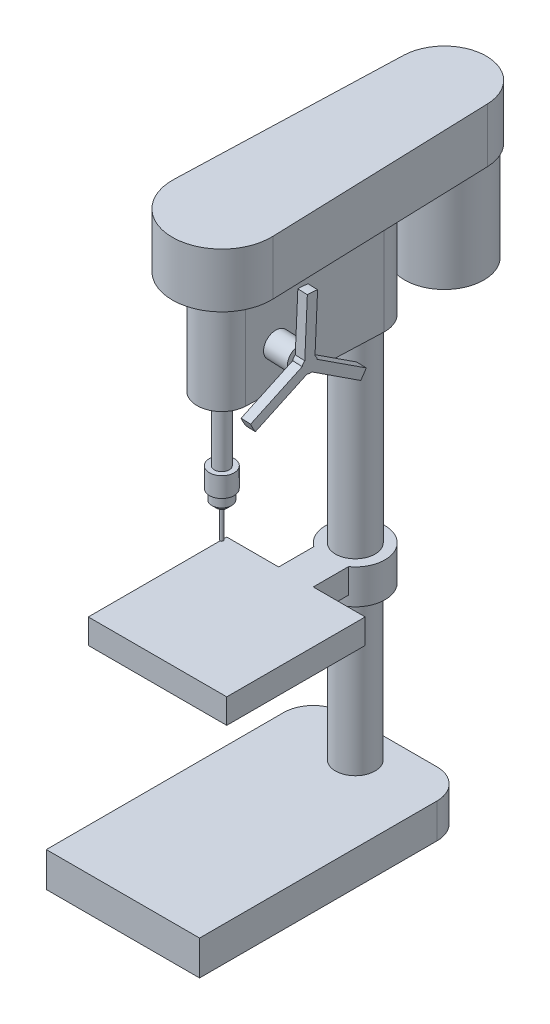
SolidWorks part; units mm, degrees
ref_plane "正面" through (0, 0, 0) normal (0, 0, 1) x (1, 0, 0)
ref_plane "平面" through (0, 0, 0) normal (0, 1, 0) x (1, 0, 0)
ref_plane "右側面" through (0, 0, 0) normal (1, 0, 0) x (0, 0, -1)
sketch "ｽｹｯﾁ1" plane through (0, 0, 0) normal (0, 1, 0) x (1, 0, 0)
  line L1 (0, 0) -> (310, 0)
  line L2 (0, 0) -> (0, 540)
  line L3 (0, 540) -> (310, 540)
  line L4 (310, 0) -> (310, 540)
  dimension "D1" = 310
  dimension "D2" = 540
extrude "ﾎﾞｽ - 押し出し1" add sketch "ｽｹｯﾁ1" along normal blind 70
fillet "ﾌｨﾚｯﾄ1" radius 60 2 edges at (0, 35, -540) (310, 35, -540)
sketch "ｽｹｯﾁ2" plane through (0, 70, 0) normal (0, 1, 0) x (1, 0, 0)
  line L0 (310, 0) -> (310, 480) construction
  line L1 (250, 540) -> (60, 540) construction
  circle A0 centre (155, 470) radius 40
  dimension "D1" = 80
  dimension "D2" = 155
  dimension "D3" = 70
extrude "ﾎﾞｽ - 押し出し2" add sketch "ｽｹｯﾁ2" along normal blind 310
sketch "ｽｹｯﾁ3" plane through (0, 380, 0) normal (0, 1, 0) x (1, 0, 0)
  circle A0 centre (155, 470) radius 60
  dimension "D1" = 120
extrude "ﾎﾞｽ - 押し出し3" add sketch "ｽｹｯﾁ3" along normal blind 20
sketch "ｽｹｯﾁ4" plane through (0, 400, 0) normal (0, 1, 0) x (1, 0, 0)
  line L0 (190, 350) -> (295, 350)
  line L1 (15, 70) -> (295, 70)
  line L2 (15, 70) -> (15, 350)
  line L3 (15, 350) -> (120, 350)
  line L4 (295, 70) -> (295, 350)
  line L6 (120, 421.266) -> (120, 350)
  line L8 (190, 421.266) -> (190, 350)
  arc A0 (190, 421.266) -> (120, 421.266) centre (155, 470) ccw
  dimension "D1" = 120
  dimension "D2" = 280
  dimension "D3" = 280
  dimension "D4" = 140
  dimension "D5" = 35
  dimension "D6" = 120
  dimension "D8" = 35
extrude "ﾎﾞｽ - 押し出し4" add sketch "ｽｹｯﾁ4" along normal blind 50
sketch "ｽｹｯﾁ5" plane through (0, 450, 0) normal (0, 1, 0) x (1, 0, 0)
  circle A0 centre (155, 470) radius 40
  dimension "D1" = 80
extrude "ﾎﾞｽ - 押し出し5" add sketch "ｽｹｯﾁ5" along normal blind 400
sketch "ｽｹｯﾁ8" plane through (0, 850, 0) normal (0, 1, 0) x (1, 0, 0)
  line L0 (95.0412, 467.7778) -> (105.0343, 198.1481)
  line L1 (214.9588, 467.7778) -> (204.9657, 198.1481)
  arc A0 (214.9588, 467.7778) -> (95.0412, 467.7778) centre (155, 470) ccw
  circle A1 centre (155, 470) radius 40 construction
  arc A2 (105.0343, 198.1481) -> (204.9657, 198.1481) centre (155, 200) ccw
  dimension "D1" = 120
  dimension "100" = 100
  dimension "D3" = 270
extrude "ﾎﾞｽ - 押し出し6" add sketch "ｽｹｯﾁ8" along normal blind 210
sketch "ｽｹｯﾁ9" plane through (0, 1060, 0) normal (0, 1, 0) x (1, 0, 0)
  line L0 (55.0556, 203.3333) -> (70.0472, 652.8333)
  line L1 (239.9528, 652.8333) -> (254.9444, 203.3333)
  arc A0 (239.9528, 652.8333) -> (70.0472, 652.8333) centre (155, 650) ccw
  arc A1 (55.0556, 203.3333) -> (254.9444, 203.3333) centre (155, 200) ccw
  arc A3 (105.0343, 198.1481) -> (204.9657, 198.1481) centre (155, 200) ccw construction
  dimension "D1" = 170
  dimension "D2" = 200
  dimension "D3" = 450
extrude "ﾎﾞｽ - 押し出し7" add sketch "ｽｹｯﾁ9" along normal blind 110
sketch "ｽｹｯﾁ10" plane through (0, 1060, 0) normal (0, -1, 0) x (-1, 0, 0)
  circle A0 centre (-155, 650) radius 80
  arc A1 (-70.0472, 652.8333) -> (-239.9528, 652.8333) centre (-155, 650) ccw construction
  dimension "D1" = 160
extrude "ﾎﾞｽ - 押し出し8" add sketch "ｽｹｯﾁ10" along normal blind 200
sketch "ｽｹｯﾁ11" plane through (0, 850, 0) normal (0, -1, 0) x (-1, 0, 0)
  circle A0 centre (-155, 200) radius 15
  arc A1 (-204.9657, 198.1481) -> (-105.0343, 198.1481) centre (-155, 200) ccw construction
  dimension "D1" = 30
extrude "ﾎﾞｽ - 押し出し9" add sketch "ｽｹｯﾁ11" along normal blind 130
sketch "ｽｹｯﾁ12" plane through (0, 720, 0) normal (0, -1, 0) x (-1, 0, 0)
  circle A0 centre (-155, 200) radius 25
  circle A1 centre (-155, 200) radius 15 construction
  dimension "D1" = 50
extrude "ﾎﾞｽ - 押し出し10" add sketch "ｽｹｯﾁ12" along normal blind 40
sketch "ｽｹｯﾁ13" plane through (0, 680, 0) normal (0, -1, 0) x (-1, 0, 0)
  circle A0 centre (-155, 200) radius 20
  circle A1 centre (-155, 200) radius 25 construction
  dimension "D1" = 40
extrude "ﾎﾞｽ - 押し出し11" add sketch "ｽｹｯﾁ13" along normal blind 30
chamfer "面取り1" distance 10 angle 45 1 edges at (155, 650, -220)
sketch "ｽｹｯﾁ14" plane through (0, 650, 0) normal (0, -1, 0) x (-1, 0, 0)
  circle A0 centre (-155, 200) radius 3.5
  circle A1 centre (-155, 200) radius 10 construction
  dimension "D1" = 7
extrude "ﾎﾞｽ - 押し出し12" add sketch "ｽｹｯﾁ14" along normal blind 60
sketch "ｽｹｯﾁ15" plane through (197.3507, 0, 7.3143) normal (0.9993, 0, 0.037) x (0.037, 0, -0.9993)
  line L0 (205.6035, 850) -> (475.4183, 850) construction
  line L1 (205.6035, 1060) -> (205.6035, 850) construction
  circle A0 centre (265.6035, 930) radius 25
  dimension "D1" = 50
  dimension "D2" = 80
  dimension "D3" = 60
extrude "ﾎﾞｽ - 押し出し13" add sketch "ｽｹｯﾁ15" along normal blind 50
sketch "ｽｹｯﾁ16" plane through (247.3164, 0, 9.1662) normal (0.9993, 0, 0.037) x (0.037, 0, -0.9993)
  circle A0 centre (265.6035, 930) radius 125
  circle A1 centre (265.6035, 930) radius 25 construction
  dimension "D1" = 250
extrude "ﾎﾞｽ - 押し出し14" add sketch "ｽｹｯﾁ16" along normal blind 20
sketch "ｽｹｯﾁ17" plane through (267.3027, 0, 9.9069) normal (0.9993, 0, 0.037) x (0.037, 0, -0.9993)
  line L0 (265.6035, 930) -> (313.5013, 899.4343) construction
  line L1 (265.6035, 930) -> (207.6336, 899.879) construction
  line L2 (265.6035, 930) -> (268.4104, 993.1809) construction
  line L3 (251.0718, 933.7187) -> (150.4279, 881.4244)
  line L5 (159.6494, 863.6772) -> (260.2932, 915.9714)
  line L6 (269.6489, 915.5558) -> (365.259, 854.5428)
  line L7 (280.4078, 932.4154) -> (376.0179, 871.4024)
  line L8 (276.0899, 940.7255) -> (281.1236, 1054.0328)
  line L9 (256.1096, 941.6131) -> (261.1433, 1054.9204)
  circle A0 centre (265.6035, 930) radius 125 construction
  arc A1 (260.2932, 915.9714) -> (269.6489, 915.5558) centre (265.6035, 930) ccw
  circle A2 centre (265.6035, 930) radius 125
  arc A3 (256.1096, 941.6131) -> (251.0718, 933.7187) centre (265.6035, 930) ccw
  arc A4 (280.4078, 932.4154) -> (276.0899, 940.7255) centre (265.6035, 930) ccw
  circle M1 centre (265.6035, 930) radius 125
  dimension "D3" = 30
  dimension "D10" = 250
  dimension "D1" = 120
  dimension "D2" = 120
  dimension "D4" = 20
  dimension "D5" = 20
  dimension "D6" = 10
  dimension "D7" = 10
  dimension "D8" = 20
  dimension "D9" = 10
extrude "ｶｯﾄ - 押し出し1" cut sketch "ｽｹｯﾁ17" against normal blind 20 contours A3 L9 L3 M1 | A4 L7 L8 M1 | A1 L5 L6 M1 region at (274.807, 970.1952, -192.5699) region at (277.0171, 855.3534, -252.2004) region at (279.5956, 964.4514, -321.7729)
